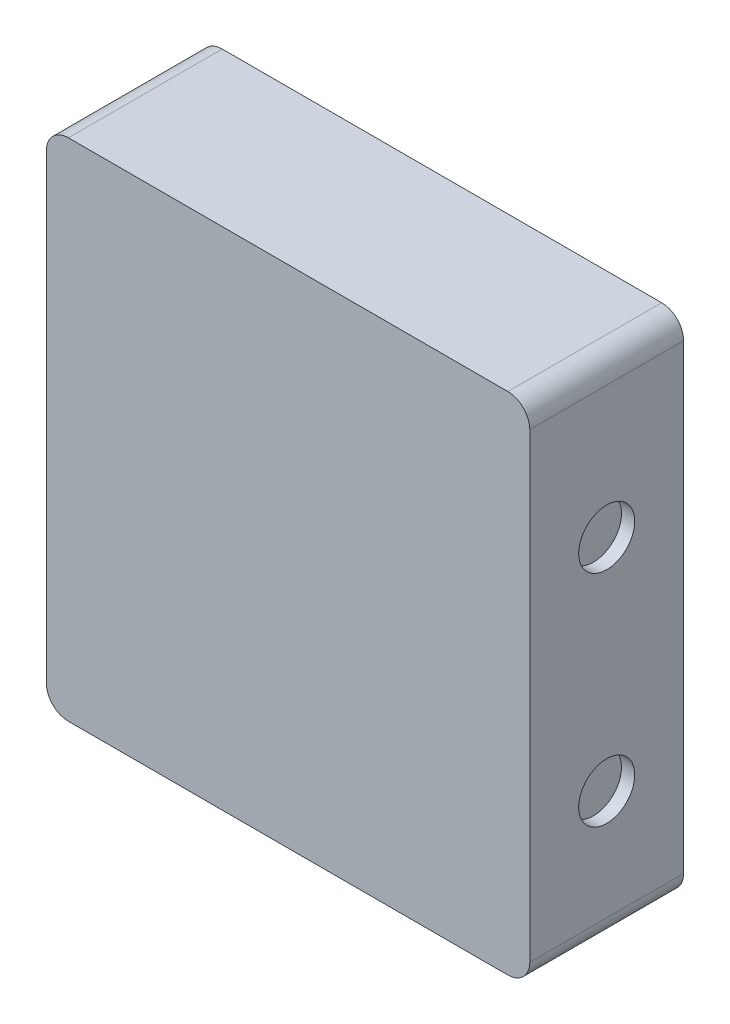
SolidWorks part; units mm, degrees
ref_plane "Front Plane" through (0, 0, 0) normal (0, 0, 1) x (1, 0, 0)
ref_plane "Top Plane" through (0, 0, 0) normal (0, 1, 0) x (1, 0, 0)
ref_plane "Right Plane" through (0, 0, 0) normal (1, 0, 0) x (0, 0, -1)
ref_plane "Plane1" through (0, 0, 31) normal (0, 0, 1) x (1, 0, 0)
sketch "Sketch1" plane through (0, 0, 31) normal (0, 0, 1) x (1, 0, 0)
  line L0 (-22, -20) -> (-22, -10.75) construction
  line L1 (-22, -10.75) -> (-22, 10.75) construction
  line L2 (-22, 10.75) -> (-22, 22) construction
  line L3 (-20, 24) -> (-3.9389, 24) construction
  line L4 (-3.9389, 24) -> (3.9389, 24) construction
  line L5 (3.9389, 24) -> (20, 24) construction
  line L6 (22, 22) -> (22, 10.75) construction
  line L7 (22, 10.75) -> (22, -10.75) construction
  line L8 (22, -10.75) -> (22, -20) construction
  line L9 (20, -22) -> (10.75, -22) construction
  line L10 (10.75, -22) -> (-10.75, -22) construction
  line L11 (-10.75, -22) -> (-20, -22) construction
  line L12 (-22, -20) -> (-22, -10.75)
  line L13 (-22, -10.75) -> (-22, 10.75)
  line L14 (-22, 10.75) -> (-22, 22)
  line L15 (-20, 24) -> (-3.9389, 24)
  line L16 (-3.9389, 24) -> (3.9389, 24)
  line L17 (3.9389, 24) -> (20, 24)
  line L18 (22, 22) -> (22, 10.75)
  line L19 (22, 10.75) -> (22, -10.75)
  line L20 (22, -10.75) -> (22, -20)
  line L21 (20, -22) -> (10.75, -22)
  line L22 (10.75, -22) -> (-10.75, -22)
  line L23 (-10.75, -22) -> (-20, -22)
  line L24 (-19, -18) -> (-19, -10.75)
  line L25 (-19, -10.75) -> (-19, 10.75)
  line L26 (-19, 10.75) -> (-19, 20)
  line L27 (-18, 21) -> (-3.9389, 21)
  line L28 (-3.9389, 21) -> (3.9389, 21)
  line L29 (3.9389, 21) -> (18, 21)
  line L30 (19, 20) -> (19, 10.75)
  line L31 (19, 10.75) -> (19, -10.75)
  line L32 (19, -10.75) -> (19, -18)
  line L33 (18, -19) -> (10.75, -19)
  line L34 (10.75, -19) -> (-10.75, -19)
  line L35 (-10.75, -19) -> (-18, -19)
  line L36 (-19, -19) -> (-19, -10.75) construction
  line L37 (-10.75, -19) -> (-19, -19) construction
  line L38 (19, -19) -> (10.75, -19) construction
  line L39 (19, -10.75) -> (19, -19) construction
  line L40 (19, 21) -> (19, 10.75) construction
  line L41 (3.9389, 21) -> (19, 21) construction
  line L42 (-19, 21) -> (-3.9389, 21) construction
  line L43 (-19, 10.75) -> (-19, 21) construction
  line L44 (-19, -18) -> (-19, -22)
  line L45 (19, -18) -> (19, -22)
  arc A0 (-20, 24) -> (-22, 22) centre (-20, 22) ccw construction
  arc A1 (22, 22) -> (20, 24) centre (20, 22) ccw construction
  arc A2 (20, -22) -> (22, -20) centre (20, -20) ccw construction
  arc A3 (-22, -20) -> (-20, -22) centre (-20, -20) ccw construction
  arc A4 (-20, 24) -> (-22, 22) centre (-20, 22) ccw
  arc A5 (22, 22) -> (20, 24) centre (20, 22) ccw
  arc A6 (20, -22) -> (22, -20) centre (20, -20) ccw
  arc A7 (-22, -20) -> (-20, -22) centre (-20, -20) ccw
  arc A12 (-19, -18) -> (-18, -19) centre (-18, -18) ccw
  arc A13 (-19, -19) -> (-19, -19) centre (-19, -19) ccw construction
  arc A14 (18, -19) -> (19, -18) centre (18, -18) ccw
  arc A15 (19, -19) -> (19, -19) centre (19, -19) ccw construction
  arc A16 (19, 20) -> (18, 21) centre (18, 20) ccw
  arc A17 (19, 21) -> (19, 21) centre (19, 21) ccw construction
  arc A18 (-18, 21) -> (-19, 20) centre (-18, 20) ccw
  arc A19 (-19, 21) -> (-19, 21) centre (-19, 21) ccw construction
  dimension "D2" = 1
  dimension "D1" = 3
extrude "Boss-Extrude4" add sketch "Sketch1" along normal blind 3 contours L12 A7 L23 L22 L21 A6 L20 L19 L18 A5 L17 L16 L15 A4 L14 L13 A18 L27 L28 L29 A16 L30 L31 L32 A14 L33 L34 L35 A12 L24 L25 L26 | L27 A18 L26 L25 L24 A12 L35 L34 L33 A14 L32 L31 L30 A16 L29 L28 | A14 L33 L34 L35 A12 L23 L22 L21 region at (-21.3634, -15.375, 31) region at (0, -20.4935, 31) region at (0, 1, 31)
extrude "Boss-Extrude5" add sketch "Sketch1<3>" along normal up to surface (14 mm away) contours L12 A7 L23 L22 L21 A6 L20 L19 L18 A5 L17 L16 L15 A4 L14 L13 A18 L27 L28 L29 A16 L30 L31 L32 A14 L33 L34 L35 A12 L24 L25 L26 region at (-21.3634, -15.375, 31)
sketch "Sketch1<3>" plane through (0, 0, 31) normal (0, 0, 1) x (1, 0, 0) same geometry as "Sketch1"
extrude "Boss-Extrude6" add sketch "Sketch1<4>" against normal blind 3 from surface contours L12 A7 L23 L22 L21 A6 L20 L19 L18 A5 L17 L16 L15 A4 L14 L13 A18 L27 L28 L29 A16 L30 L31 L32 A14 L33 L34 L35 A12 L24 L25 L26 | L27 A18 L26 L25 L24 A12 L35 L34 L33 A14 L32 L31 L30 A16 L29 L28 | A14 L33 L34 L35 A12 L23 L22 L21 region at (-21.3634, -15.375, 31) region at (0, -20.4935, 31) region at (0, 1, 31) starting at face at (0, 3.3153, 45)
sketch "Sketch1<4>" plane through (0, 0, 31) normal (0, 0, 1) x (1, 0, 0) same geometry as "Sketch1"
sketch "Sketch2" plane through (0, -22, 0) normal (0, -1, 0) x (1, 0, 0)
  line L0 (-5, 37) -> (-5, 30.5)
  line L2 (-10.75, 30.5) -> (10.75, 30.5) construction
  line L4 (-5, 30.5) -> (5, 30.5)
  line L5 (5, 30.5) -> (5, 37)
  line L6 (5, 45) -> (-5, 45)
  line L7 (5, 37) -> (5, 45)
  line L8 (-5, 37) -> (5, 37)
  line L9 (-5, 45) -> (-5, 37)
  line L10 (5, 45) -> (-5, 45) construction
  line L11 (5, 37) -> (5, 45) construction
  line L12 (-5, 37) -> (5, 37)
  line L13 (-5, 45) -> (-5, 37) construction
  line M10 (19, 34) -> (-19, 34)
  line M13 (-20, 31) -> (20, 31)
  dimension "D1" = 0
extrude "Cut-Extrude1" cut sketch "Sketch2" against normal blind 3 contours L5 L0 M13 M10 | L12 L0 L5 M10 region at (0, -22, 35.5) region at (0, -22, 32.5)
sketch "Sketch3" plane through (0, 0, 0) normal (1, 0, 0) x (0, 0, -1)
  circle A0 centre (-38, -10) radius 2.55 construction
  circle A1 centre (-38, 10) radius 2.55 construction
  circle A2 centre (-38, -10) radius 2.55
  circle A3 centre (-38, 10) radius 2.55
extrude "Cut-Extrude2" cut sketch "Sketch3" against normal blind 1.2 from surface contours A3 | A2 region at (0, -10, 38) region at (0, 10, 38) starting at face at (22, 1, 38)
extrude "Cut-Extrude3" cut sketch "Sketch3<3>" along normal blind 1.2 from surface contours A2 | A3 region at (0, -10, 38) region at (0, 10, 38) starting at face at (-22, 1, 38)
sketch "Sketch3<3>" plane through (0, 0, 0) normal (1, 0, 0) x (0, 0, -1) same geometry as "Sketch3"
fillet "Fillet1" radius 0.7 23 edges at (12, -22, 34) (5, -20.5, 34) (-12, -22, 34) (19, -22, 38) (-5, -20.5, 31) (5, -20.5, 31) (0, -19, 34) (-19, -22, 38) (19, -1, 34) (18.7071, 20.7071, 34) (0, 21, 34) (-18.7071, 20.7071, 34) (19, -1, 42) (18.7071, 20.7071, 42) (0, 21, 42) (-18.7071, 20.7071, 42) (0, -19, 31) (-5, -20.5, 34) (0, -22, 42) (-19, -1, 34) (-19, -1, 42) (5, -19, 32.5) (-5, -19, 32.5)
